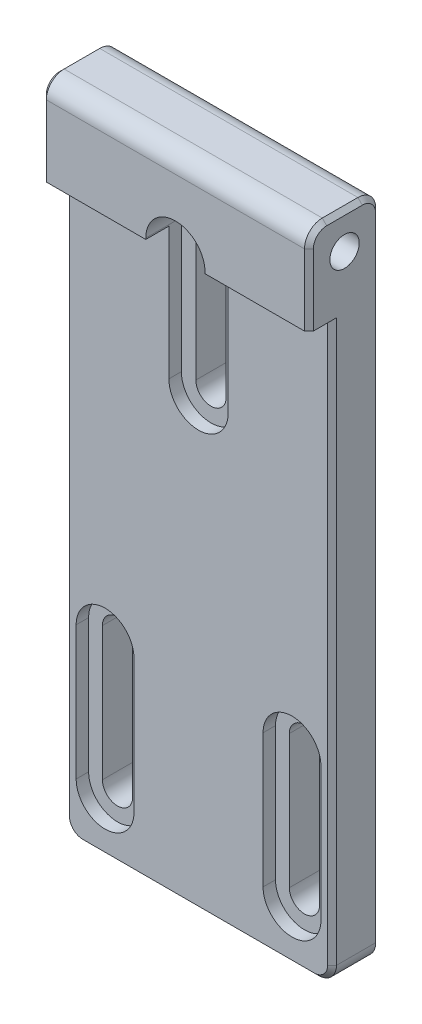
SolidWorks part; units mm, degrees
ref_plane "Front Plane" through (0, 0, 0) normal (0, 0, 1) x (1, 0, 0)
ref_plane "Top Plane" through (0, 0, 0) normal (0, 1, 0) x (1, 0, 0)
ref_plane "Right Plane" through (0, 0, 0) normal (1, 0, 0) x (0, 0, -1)
sketch "Sketch1" plane through (0, 0, 0) normal (0, 0, 1) x (1, 0, 0)
  line L1 (-15, 40) -> (15, 40)
  line L2 (-15, 40) -> (-15, -40)
  line L3 (-15, -40) -> (15, -40)
  line L4 (15, 40) -> (15, -40)
  line L5 (-15, 40) -> (15, -40) construction
  line L6 (-15, -40) -> (15, 40) construction
  point P0 (0, 0)
  dimension "D1" = 30
  dimension "D2" = 80
extrude "Boss-Extrude1" add sketch "Sketch1" along normal blind 8
hole_wizard "M4 Tapped Hole1" positions "Sketch2" profile "Sketch3" tap size "M4" standard "DIN"
sketch "Sketch2" plane through (-15, 0, 0) normal (-1, 0, 0) x (0, 0, 1)
  line L0 (8, 40) -> (0, 40) construction
  line L1 (0, 40) -> (0, -40) construction
  point P0 (4, 36)
  dimension "D1" = 4
  dimension "D2" = 4
sketch "Sketch3" plane through (-15, 36, 4) normal (0, 1, 0) x (0, 0, 1)
  line L0 (0, 0) -> (0, 12.4914)
  line L1 (0, 12.4914) -> (1.65, 11.5)
  line L2 (1.65, 11.5) -> (1.65, 0)
  line L5 (1.65, 0) -> (0, 0)
  line L10 (0, 12.4914) -> (-1.65, 11.5) construction
  line L11 (0, -6.35) -> (0, 107.95) construction
  dimension "Tap Drill Dia." = 3.3
  dimension "Tap Drill Depth" = 11.5
  dimension "Drill Angle" = 118
cosmetic thread "Hole Thread1" parameters "D1"=8, "D2"=4
ref_plane "Plane1" through (0, 0, 0) normal (-1, 0, 0) x (0, 0, 1)
mirror "Mirror1" about plane through (0, 0, 0) normal (-1, 0, 0) of "M4 Tapped Hole1"
sketch "Sketch4" plane through (0, 0, 0) normal (0, 0, -1) x (-1, 0, 0)
  line L0 (-10.5, -14) -> (-10.5, -29) construction
  line L1 (-8.8, -14) -> (-8.8, -29)
  line L2 (-12.2, -14) -> (-12.2, -29)
  line L3 (0, 44.8693) -> (0, 19.2939) construction
  line L4 (15, -40) -> (-15, -40) construction
  line L5 (10.5, -14) -> (10.5, -29) construction
  line L6 (8.8, -14) -> (8.8, -29)
  line L7 (12.2, -14) -> (12.2, -29)
  arc A0 (-8.8, -14) -> (-12.2, -14) centre (-10.5, -14) ccw
  arc A1 (-12.2, -29) -> (-8.8, -29) centre (-10.5, -29) ccw
  arc A2 (8.8, -14) -> (12.2, -14) centre (10.5, -14) cw
  arc A3 (12.2, -29) -> (8.8, -29) centre (10.5, -29) cw
  point P2 (-10.5, -21.5)
  point P14 (10.5, -21.5)
  dimension "D1" = 11
  dimension "D2" = 10.5
  dimension "D3" = 15
extrude "Cut-Extrude1" cut sketch "Sketch4" against normal through all
sketch "Sketch5" plane through (0, 0, 8) normal (0, 0, 1) x (1, 0, 0)
  line L0 (-10.5, -14) -> (-10.5, -29) construction
  line L1 (-7.25, -14) -> (-7.25, -29)
  line L2 (-13.75, -14) -> (-13.75, -29)
  line L3 (0, 47.9266) -> (0, 22.8566) construction
  line L4 (10.5, -14) -> (10.5, -29) construction
  line L5 (7.25, -14) -> (7.25, -29)
  line L6 (13.75, -14) -> (13.75, -29)
  arc A0 (-7.25, -14) -> (-13.75, -14) centre (-10.5, -14) ccw
  arc A1 (-13.75, -29) -> (-7.25, -29) centre (-10.5, -29) ccw
  arc A2 (7.25, -14) -> (13.75, -14) centre (10.5, -14) cw
  arc A3 (13.75, -29) -> (7.25, -29) centre (10.5, -29) cw
  point P4 (-10.5, -21.5)
  point P14 (10.5, -21.5)
extrude "Cut-Extrude2" cut sketch "Sketch5" against normal blind 4
sketch "Sketch6" plane through (0, 0, 8) normal (0, 0, 1) x (1, 0, 0)
  line L0 (0, 30.14) -> (0, 15.14) construction
  line L1 (1.7, 30.14) -> (1.7, 15.14)
  line L2 (-1.7, 30.14) -> (-1.7, 15.14)
  arc A0 (1.7, 30.14) -> (-1.7, 30.14) centre (0, 30.14) ccw
  arc A1 (-1.7, 15.14) -> (1.7, 15.14) centre (0, 15.14) ccw
  arc A2 (-8.8, -14) -> (-12.2, -14) centre (-10.5, -14) ccw construction
  point P3 (0, 22.64)
  dimension "D1" = 44.14
  dimension "D2" = 15
extrude "Cut-Extrude3" cut sketch "Sketch6" against normal blind 32
sketch "Sketch7" plane through (0, 0, 8) normal (0, 0, 1) x (1, 0, 0)
  line L0 (0, 30.14) -> (0, 15.14) construction
  line L1 (3.3298, 30.14) -> (3.3298, 15.14)
  line L2 (-3.3298, 30.14) -> (-3.3298, 15.14)
  arc A0 (3.3298, 30.14) -> (-3.3298, 30.14) centre (0, 30.14) ccw
  arc A1 (-3.3298, 15.14) -> (3.3298, 15.14) centre (0, 15.14) ccw
  point P4 (0, 22.64)
extrude "Cut-Extrude4" cut sketch "Sketch7" against normal blind 4
sketch "Sketch8" plane through (-15, 0, 0) normal (-1, 0, 0) x (0, 0, 1)
  line L0 (8, 40) -> (0, 40) construction
  line L1 (8, -40) -> (5.4, -40)
  line L2 (8, -40) -> (8, 30)
  line L3 (8, 30) -> (5.4, 30)
  line L4 (5.4, -40) -> (5.4, 30)
  dimension "D1" = 2.6
  dimension "D2" = 10
extrude "Cut-Extrude5" cut sketch "Sketch8" against normal blind 73
fillet "Fillet1" radius 2 2 edges at (0, 40, 8) (0, 40, 0)
fillet "Fillet2" radius 2 2 edges at (-15, -40, 2.7) (15, -40, 2.7)
chamfer "Chamfer1" distance 0.5 angle 45 18 edges at (-15, -4, 5.4) (-14.4142, -39.4142, 5.4) (0, -40, 5.4) (14.4142, -39.4142, 5.4) (15, -4, 5.4) (-15, 34, 8) (15, 34, 8) (-15, 39.4142, 7.4142) (15, 39.4142, 7.4142) (-15, 40, 4) (15, 40, 4) (-15, 39.4142, 0.5858) (15, 39.4142, 0.5858) (-15, 0, 0) (-14.4142, -39.4142, 0) (0, -40, 0) (14.4142, -39.4142, 0) (15, 0, 0)
sketch "Sketch9" plane through (0, 0, 0) normal (0, 0, -1) x (-1, 0, 0)
  line L0 (13, -40) -> (-13, -40) construction
  line L1 (-5, -40) -> (5, -40)
  line L2 (-5, -40) -> (-5, -22.5)
  line L3 (-3.5, -21) -> (3.5, -21)
  line L4 (5, -40) -> (5, -22.5)
  line L5 (15, 38) -> (15, -38) construction
  line L6 (-15, -38) -> (-15, 38) construction
  arc A1 (3.5, -21) -> (5, -22.5) centre (3.5, -22.5) cw
  arc A2 (-3.5, -21) -> (-5, -22.5) centre (-3.5, -22.5) ccw
  point P14 (-5, -21)
  dimension "D4" = 1.5
  dimension "D1" = 19
  dimension "D2" = 10
  dimension "D3" = 10
extrude "Cut-Extrude7" cut sketch "Sketch9" against normal blind 1
sketch "Sketch10" plane through (0, 0, 5.4) normal (0, 0, 1) x (1, 0, 0)
  line L1 (-20.2354, -35) -> (21.3985, -35)
  line L2 (-20.2354, -35) -> (-20.2354, -40)
  line L3 (-20.2354, -40) -> (21.3985, -40)
  line L4 (21.3985, -35) -> (21.3985, -40)
  dimension "D1" = 5
extrude "Cut-Extrude8" cut sketch "Sketch10" against normal blind 10
fillet "Fillet3" radius 2 2 edges at (15, -35, 2.7) (-15, -35, 2.7)
chamfer "Chamfer2" distance 0.5 angle 45 7 edges at (13.8229, -34.8229, 0) (9, -35, 0) (13.8229, -34.8229, 5.4) (-13.8229, -34.8229, 5.4) (0, -35, 5.4) (-13.8229, -34.8229, 0) (-9, -35, 0)
